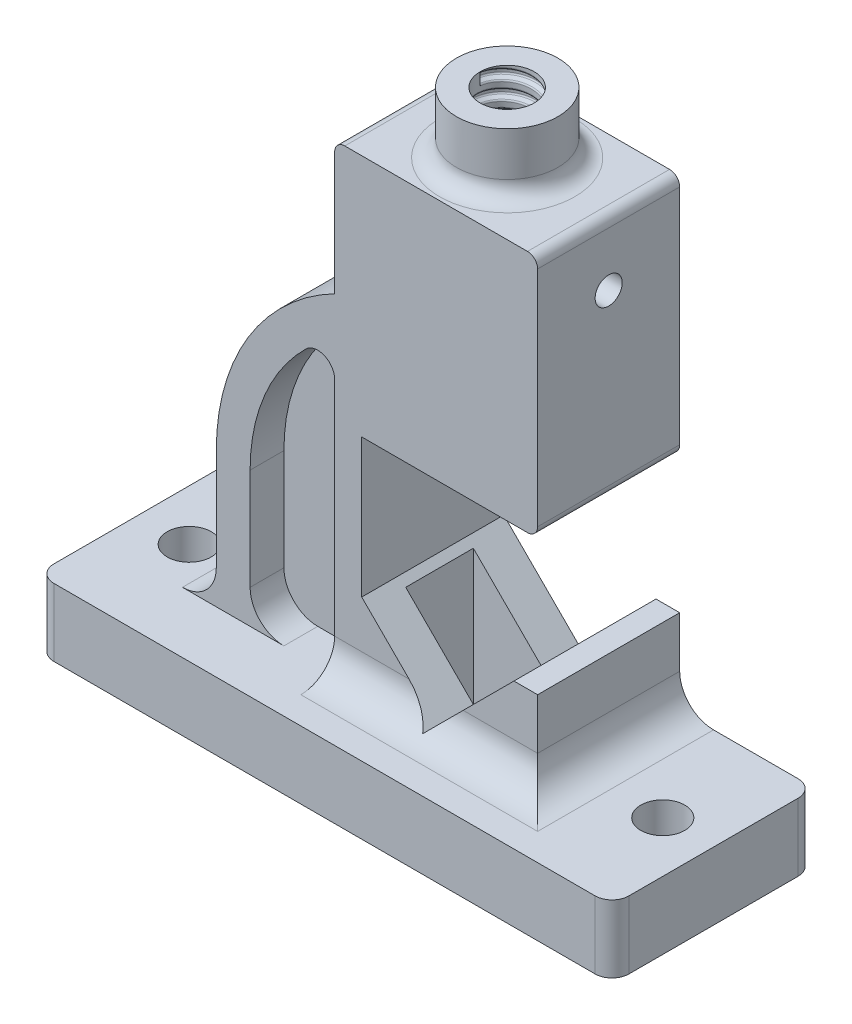
SolidWorks part; units mm, degrees
ref_plane "Front Plane" through (0, 0, 0) normal (0, 0, 1) x (1, 0, 0)
ref_plane "Top Plane" through (0, 0, 0) normal (0, 1, 0) x (1, 0, 0)
ref_plane "Right Plane" through (0, 0, 0) normal (1, 0, 0) x (0, 0, -1)
sketch "Sketch1" plane through (0, 0, 0) normal (0, 1, 0) x (1, 0, 0)
  line L1 (-85, -30) -> (85, -30)
  line L2 (-85, -30) -> (-85, 30)
  line L3 (-85, 30) -> (85, 30)
  line L4 (85, -30) -> (85, 30)
  line L5 (-85, -30) -> (85, 30) construction
  line L6 (-85, 30) -> (85, -30) construction
  point P0 (0, 0)
  dimension "D1" = 170
  dimension "D2" = 60
extrude "Boss-Extrude1" add sketch "Sketch1" along normal blind 20
fillet "Fillet2" radius 5 4 edges at (85, 10, 30) (-85, 10, -30) (85, 10, -30) (-85, 10, 30)
sketch "Sketch2" plane through (0, 20, 0) normal (0, 1, 0) x (1, 0, 0)
  line L0 (0, 39.2225) -> (0, -62.5194) construction
  line L1 (-85, 25) -> (-85, -25) construction
  circle A0 centre (-70, 0) radius 6.5
  circle A1 centre (70, 0) radius 6.5
  dimension "D1" = 13
  dimension "D2" = 15
extrude "Cut-Extrude1" cut sketch "Sketch2" against normal up to next
sketch "Sketch3" plane through (0, 0, 0) normal (0, 0, 1) x (1, 0, 0)
  line L0 (15, 20) -> (15, 85) construction
  line L1 (-80, 20) -> (80, 20) construction
  line L2 (-7, 20) -> (-7, 85)
  line L3 (-7, 85) -> (45, 85)
  line L4 (45, 85) -> (45, 157)
  line L5 (45, 157) -> (-15, 157)
  line L6 (-7, 20) -> (-50, 20)
  line L7 (-50, 20) -> (-50, 60)
  line L8 (-15, 117.6628) -> (-15, 157)
  line L9 (85, 20) -> (85, 0) construction
  line L10 (-80, 0) -> (80, 0) construction
  arc A1 (-50, 60) -> (-15, 117.6628) centre (15, 60) cw
  point P13 (15, 52.5)
  dimension "D6" = 135
  dimension "D7" = 65
  dimension "D1" = 70
  dimension "D2" = 22
  dimension "D3" = 65
  dimension "D4" = 72
  dimension "D5" = 60
  dimension "D8" = 60
  dimension "D9" = 30
extrude "Boss-Extrude3" add sketch "Sketch3" along normal blind 42 from surface starting at face at (0, 10, -30)
sketch "Sketch4" plane through (0, 0, 12) normal (0, 0, 1) x (1, 0, 0)
  line L12 (-40, 60) -> (-40, 20)
  line L13 (-40, 60) -> (-40, 20)
  line L14 (-40, 20) -> (-15, 20)
  line L15 (-15, 20) -> (-15, 85)
  line L16 (-15, 20) -> (-15, 95.7071)
  arc A6 (-15, 95.7071) -> (-23.5, 99.2779) centre (-20, 95.7071) ccw
  arc A7 (-10.3846, 108.7916) -> (-40, 60) centre (15, 60) ccw
  arc A8 (-23.5, 99.2779) -> (-40, 60) centre (15, 60) ccw
  dimension "D3" = 5
  dimension "D1" = 10
  dimension "D2" = 8
extrude "Cut-Extrude3" cut sketch "Sketch4" against normal blind 10
ref_plane "Plane4" through (0, 0, -9) normal (0, 0, 1) x (1, 0, 0)
mirror "Mirror2" about plane through (0, 0, -9) normal (0, 0, 1) of "Cut-Extrude3"
sketch "Sketch7" plane through (0, 0, -9) normal (0, 0, 1) x (1, 0, 0)
  line L0 (15, 85) -> (15, 20) construction
  line L1 (-7, 85) -> (45, 85) construction
  line L2 (-80, 20) -> (80, 20) construction
  line L3 (85, 20) -> (85, 0) construction
  line L4 (15, 22) -> (38, 45)
  line L5 (15, 22) -> (-8, 45)
  line L6 (38, 45) -> (45, 45)
  line L7 (-8, 45) -> (-15, 45)
  line L8 (45, 45) -> (45, 20)
  line L9 (45, 20) -> (-15, 20)
  line L10 (-15, 45) -> (-15, 20)
  dimension "D1" = 70
  dimension "D2" = 90
  dimension "D3" = 25
  dimension "D4" = 2
  dimension "D5" = 60
extrude "Boss-Extrude4" add sketch "Sketch7" along normal mid plane 42
sketch "Sketch8" plane through (0, 157, 0) normal (0, 1, 0) x (1, 0, 0)
  line L0 (15, 30) -> (15, 9) construction
  line L1 (45, 30) -> (-15, 30) construction
  line L3 (-15, -12) -> (-15, 30) construction
  circle A2 centre (15, 9) radius 15
  circle A3 centre (15, 9) radius 8
  dimension "D1" = 30
  dimension "D2" = 16
  dimension "D3" = 21
extrude "Boss-Extrude5" add sketch "Sketch8" along normal blind 18
sketch "Sketch10" plane through (0, 85, 0) normal (0, -1, 0) x (1, 0, 0)
  line L1 (-7, 12) -> (45, 12) construction
  line L2 (35, -19) -> (-5, -19)
  line L3 (35, -19) -> (35, 1)
  line L4 (35, 1) -> (-5, 1)
  line L5 (-5, -19) -> (-5, 1)
  line L6 (35, -19) -> (-5, 1) construction
  line L7 (35, 1) -> (-5, -19) construction
  line L11 (45, 12) -> (45, -30) construction
  point P14 (35, -9)
  dimension "D1" = 40
  dimension "D2" = 10
  dimension "D3" = 20
  dimension "D4" = 21
extrude "Cut-Extrude4" cut sketch "Sketch10" against normal offset from surface (62 mm away) 10 up to face at (15, 157, -24)
extrude "Cut-Extrude5" cut sketch "Sketch8<2>" against normal up to surface (10 mm away) contours A3 up to face at (15, 147, -9)
sketch "Sketch8<2>" plane through (0, 157, 0) normal (0, 1, 0) x (1, 0, 0) same geometry as "Sketch8"
sketch "Sketch11" plane through (0, 45, 0) normal (0, 1, 0) x (1, 0, 0)
  line L0 (15, -12) -> (15, 30) construction
  line L1 (-5, -1) -> (35, -1)
  line L2 (-5, -1) -> (-5, 19)
  line L3 (-5, 19) -> (35, 19)
  line L4 (35, -1) -> (35, 19)
  line L5 (-5, -1) -> (35, 19) construction
  line L6 (-5, 19) -> (35, -1) construction
  point P0 (15, 9)
  dimension "D1" = 40
  dimension "D2" = 20
extrude "Cut-Extrude6" cut sketch "Sketch11" against normal through all
fillet "Fillet3" radius 5 1 edges at (15, 157, -24)
fillet "Fillet9" radius 10 4 edges at (-50, 20, -9) (45, 20, -9) (15, 20, 12) (-40, 20, 7)
thread "Thread3" pitch 5.08 method cut profile "Thread Profile4" start angle 0, offset 0, length 28, pitch 5.08, diameter 16
ref_plane "Plane8" through (7, 175, -9) normal (0, 0, 1) x (-1, 0, 0)
sketch "Thread Profile4" plane through (7, 175, -9) normal (0, 0, 1) x (-1, 0, 0)
  line L0 (0, 0) -> (0, 5.08) construction
  line L1 (0, 0) -> (0, 3.6346)
  line L2 (0.508, 3.6346) -> (1.524, 3.6346) construction
  line L3 (1.524, 2.1681) -> (1.524, 1.4665)
  line L4 (1.27, 2.6081) -> (0.254, 3.1946)
  line L5 (1.27, 1.0265) -> (0.254, 0.4399)
  line L6 (0.508, 0) -> (1.524, 0) construction
  arc A0 (0.254, 3.1946) -> (0, 3.6346) centre (0.508, 3.6346) cw
  arc A1 (0.254, 0.4399) -> (0, 0) centre (0.508, 0) ccw
  arc A2 (1.524, 1.4665) -> (1.27, 1.0265) centre (1.016, 1.4665) cw
  arc A3 (1.524, 2.1681) -> (1.27, 2.6081) centre (1.016, 2.1681) ccw
  point P10 (1.524, 2.4614)
  point P17 (1.524, 1.1732)
  point P18 (0, 3.3413)
  point P19 (0, 0.2933)
  point P20 (0, 0)
  dimension "RootFillet1" = 0.508
  dimension "RootFillet2" = 0.508
  dimension "CrestFillet2" = 0.508
  dimension "CrestFillet1" = 0.508
  dimension "Pitch" = 5.08
  dimension "Angle1" = 30
  dimension "Angle2" = 30
  dimension "a" = 3.048
  dimension "b" = 1.524
  dimension "c" = 1.2882
sketch "Sketch12" plane through (45, 0, 0) normal (1, 0, 0) x (0, 0, -1)
  line L0 (-12, 157) -> (30, 157) construction
  line L1 (9, 175) -> (9, 85) construction
  line L2 (-12, 85) -> (-12, 157) construction
  line L3 (30, 85) -> (30, 157) construction
  line L4 (24, 175) -> (-6, 175) construction
  line L5 (-12, 85) -> (30, 85) construction
  circle A0 centre (9, 138) radius 4
  dimension "D1" = 8
  dimension "D2" = 19
extrude "Cut-Extrude7" cut sketch "Sketch12" against normal through all
fillet "Fillet10" radius 3 2 edges at (45, 157, -9) (-15, 157, -9)
fillet "Fillet11" radius 3 1 edges at (45, 85, -9)
